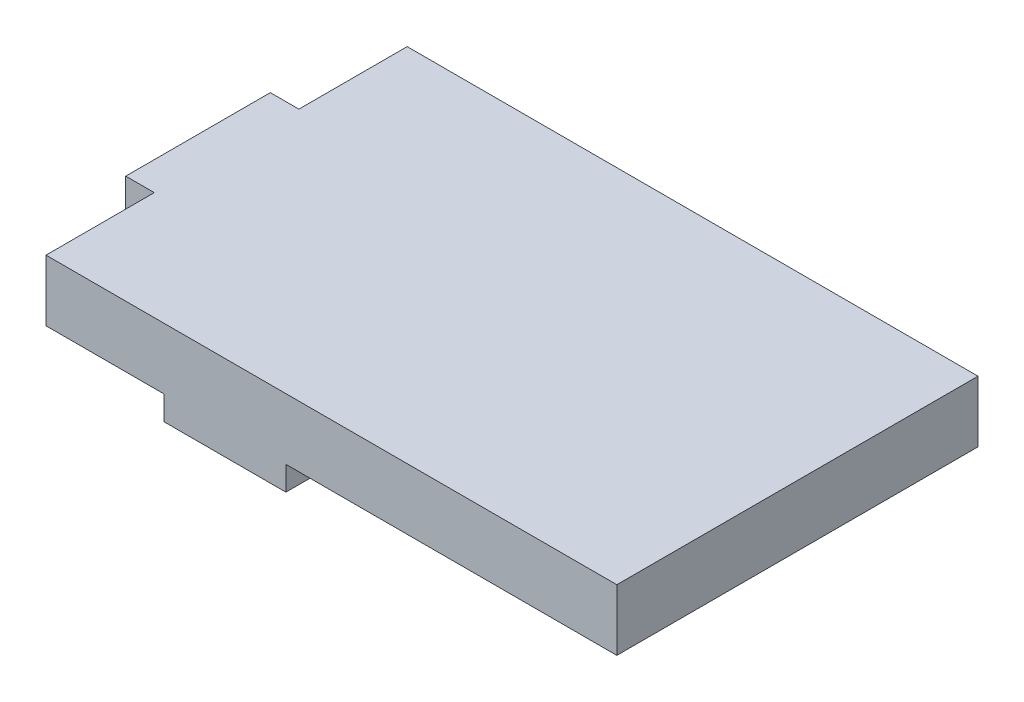
SolidWorks part; units mm, degrees
ref_plane "Front Plane" through (0, 0, 0) normal (0, 0, 1) x (1, 0, 0)
ref_plane "Top Plane" through (0, 0, 0) normal (0, 1, 0) x (1, 0, 0)
ref_plane "Right Plane" through (0, 0, 0) normal (1, 0, 0) x (0, 0, -1)
sketch "Sketch1" plane through (0, 0, 0) normal (0, 1, 0) x (1, 0, 0)
  line L1 (0, -14.986) -> (47.371, -14.986)
  line L2 (0, -14.986) -> (0, 14.986)
  line L3 (0, 14.986) -> (47.371, 14.986)
  line L4 (47.371, -14.986) -> (47.371, 14.986)
  line L5 (0, -6) -> (-18.415, -6)
  line L6 (0, -6) -> (0, 6)
  line L7 (0, 6) -> (-18.415, 6)
  line L8 (-18.415, -6) -> (-18.415, 6)
  point P11 (0, 0)
  point P12 (-18.415, 0)
  dimension "D1" = 29.972
  dimension "D2" = 47.371
  dimension "D3" = 18.415
  dimension "D4" = 12
extrude "Boss-Extrude1" add sketch "Sketch1" along normal blind 5.08 contours L1 L4 L3 L2 | L8 L5 L2 L7 region at (23.6855, 0, 0) region at (-9.2075, 0, 0)
sketch "Sketch2" plane through (0, 0, 0) normal (0, 1, 0) x (1, 0, 0)
  line L1 (9.8, -14.986) -> (19.91, -14.986)
  line L2 (9.8, -14.986) -> (9.8, -10.356)
  line L3 (9.8, -10.356) -> (19.91, -10.356)
  line L4 (19.91, -14.986) -> (19.91, -10.356)
  line L8 (0, -14.986) -> (47.371, -14.986)
  line L9 (0, -6) -> (0, -14.986)
  line L10 (-18.415, -6) -> (0, -6)
  line L11 (-18.415, 6) -> (-18.415, -6)
  line L12 (0, 6) -> (-18.415, 6)
  line L13 (0, 14.986) -> (0, 6)
  line L14 (47.371, 14.986) -> (0, 14.986)
  line L15 (47.371, -14.986) -> (47.371, 14.986)
  line L16 (0, -14.986) -> (47.371, -14.986) construction
  line L17 (0, -6) -> (0, -14.986) construction
  line L18 (-18.415, -6) -> (0, -6) construction
  line L19 (-18.415, 6) -> (-18.415, -6) construction
  line L20 (0, 6) -> (-18.415, 6) construction
  line L21 (0, 14.986) -> (0, 6) construction
  line L22 (47.371, 14.986) -> (0, 14.986) construction
  line L23 (47.371, -14.986) -> (47.371, 14.986) construction
  dimension "D2" = 9.8
  dimension "D3" = 10.11
  dimension "D4" = 4.63
  dimension "D1" = 0
extrude "Boss-Extrude2" add sketch "Sketch2" against normal blind 2
sketch "Sketch3" plane through (0, 0, 0) normal (0, 1, 0) x (1, 0, 0)
  line L1 (-18.415, 6) -> (-2.37, 6)
  line L2 (-18.415, 6) -> (-18.415, -6)
  line L3 (-18.415, -6) -> (-2.37, -6)
  line L4 (-2.37, 6) -> (-2.37, -6)
  line L8 (0, -14.986) -> (47.371, -14.986)
  line L9 (47.371, -14.986) -> (47.371, 14.986)
  line L10 (47.371, 14.986) -> (0, 14.986)
  line L11 (0, 14.986) -> (0, 6)
  line L12 (0, 6) -> (-18.415, 6)
  line L13 (-18.415, 6) -> (-18.415, -6)
  line L14 (-18.415, -6) -> (0, -6)
  line L15 (0, -6) -> (0, -14.986)
  line L16 (0, -14.986) -> (47.371, -14.986)
  line L17 (47.371, -14.986) -> (47.371, 14.986)
  line L18 (47.371, 14.986) -> (0, 14.986)
  line L19 (0, 14.986) -> (0, 6)
  line L20 (0, 6) -> (-18.415, 6)
  line L21 (-18.415, 6) -> (-18.415, -6)
  line L22 (-18.415, -6) -> (0, -6)
  line L23 (0, -6) -> (0, -14.986)
  dimension "D2" = 2.37
  dimension "D1" = 0
extrude "Cut-Extrude1" cut sketch "Sketch3" along normal through all both and the other way through all contours L4 L1 L2 L3 region at (-10.3925, 0, 0)
ref_plane "Midplane" through (22.5005, 0, 0) normal (-1, 0, 0) x (0, 0, 1)
ref_axis "Axis2" through (22.5005, 5.434, 0) along (0, -1, 0)
ref_point "Point2"
